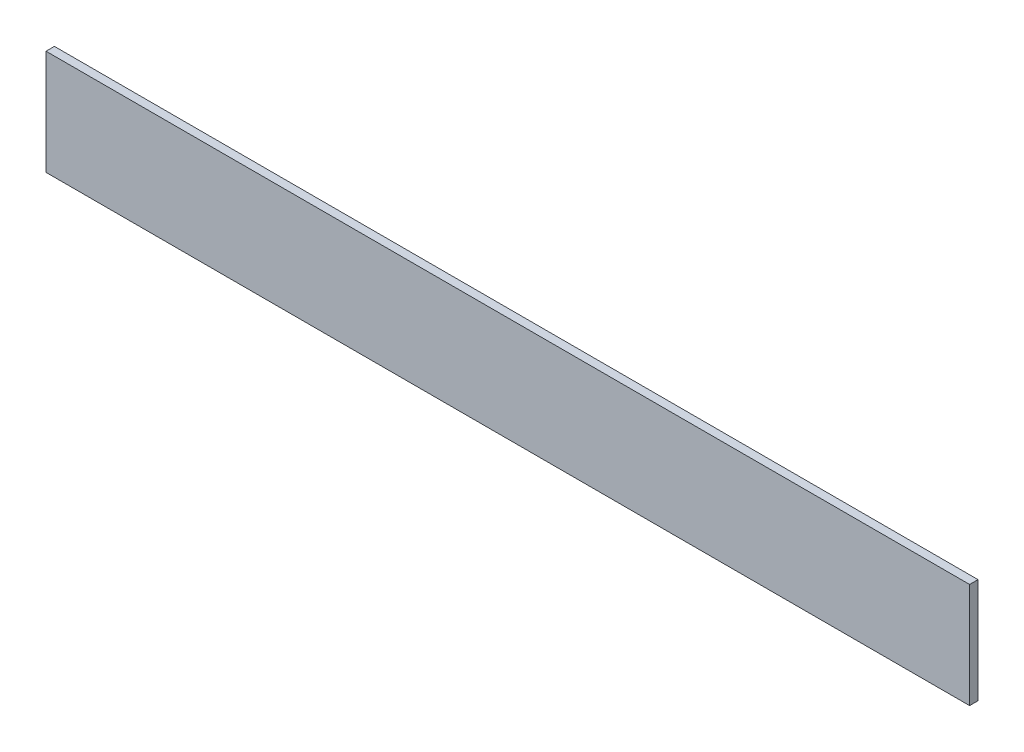
SolidWorks part; units mm, degrees
ref_plane "Спереди" through (0, 0, 0) normal (0, 0, 1) x (1, 0, 0)
ref_plane "Сверху" through (0, 0, 0) normal (0, 1, 0) x (1, 0, 0)
ref_plane "Справа" through (0, 0, 0) normal (1, 0, 0) x (0, 0, -1)
sketch "Эскиз1" plane through (0, 0, 0) normal (1, 0, 0) x (0, 0, -1)
  line L0 (0, 25) -> (0, 0)
  line L1 (0, 0) -> (25, 0)
extrude "Вытянуть-Тонкостенный1" add sketch "Эскиз1" along normal blind 220 thin thin type one direction reverse wall 2
sketch "Эскиз2" plane through (0, 0, 0) normal (0, -1, 0) x (1, 0, 0)
  line L0 (220, -25) -> (0, -25) construction
  line L1 (197, -25) -> (220, -25)
  line L2 (197, -25) -> (197, -2)
  line L3 (197, -2) -> (220, -2)
  line L4 (220, -25) -> (220, -2)
  line L5 (220, 0) -> (220, -25) construction
  dimension "D1" = 23
extrude "Вырез-Вытянуть1" cut sketch "Эскиз2" against normal through all
